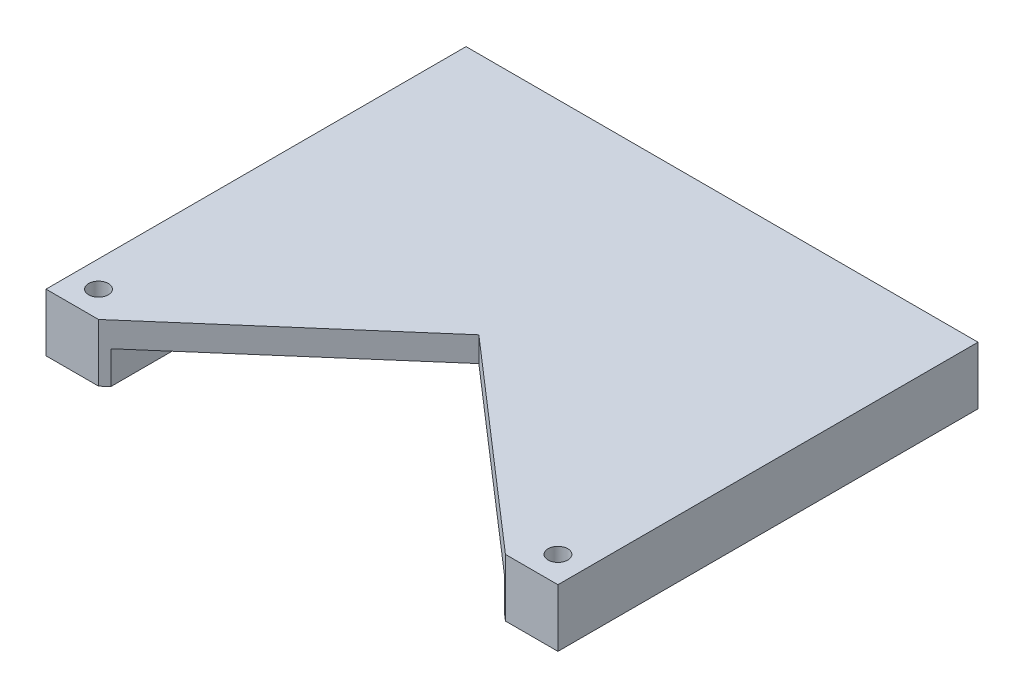
SolidWorks part; units mm, degrees
ref_plane "Front Plane" through (0, 0, 0) normal (0, 0, 1) x (1, 0, 0)
ref_plane "Top Plane" through (0, 0, 0) normal (0, 1, 0) x (1, 0, 0)
ref_plane "Right Plane" through (0, 0, 0) normal (1, 0, 0) x (0, 0, -1)
sketch "Sketch1" plane through (0, 0, 0) normal (0, 1, 0) x (1, 0, 0)
  line L1 (0, 0) -> (78, 0)
  line L2 (0, 0) -> (0, 64)
  line L3 (0, 64) -> (78, 64)
  line L4 (78, 0) -> (78, 64)
  dimension "D1" = 64
  dimension "D2" = 78
extrude "Boss-Extrude1" add sketch "Sketch1" along normal blind 8.8
sketch "Sketch2" plane through (0, 0, 0) normal (0, -1, 0) x (1, 0, 0)
  line L0 (78, -64) -> (0, -64) construction
  line L1 (6, -64) -> (72, -64)
  line L2 (6, -64) -> (6, -15)
  line L3 (6, -15) -> (72, -15)
  line L4 (72, -64) -> (72, -15)
  line L5 (0, -64) -> (0, 0) construction
  line L6 (78, 0) -> (78, -64) construction
  dimension "D1" = 6
  dimension "D2" = 6
  dimension "D3" = 49
extrude "Cut-Extrude1" cut sketch "Sketch2" against normal blind 5
sketch "Sketch3" plane through (0, 0, 0) normal (0, -1, 0) x (1, 0, 0)
  line L0 (72, -15) -> (6, -15) construction
  line L1 (9, -15) -> (69, -15)
  line L2 (9, -15) -> (9, 0)
  line L3 (9, 0) -> (69, 0)
  line L4 (69, -15) -> (69, 0)
  line L5 (0, 0) -> (78, 0) construction
  line L6 (0, -64) -> (0, 0) construction
  line L7 (78, 0) -> (78, -64) construction
  dimension "D1" = 9
  dimension "D2" = 9
extrude "Cut-Extrude2" cut sketch "Sketch3" against normal up to surface (5 mm away) up to face at (39, 5, -39.5)
sketch "Sketch4" plane through (0, 8.8, 0) normal (0, 1, 0) x (1, 0, 0)
  line L0 (0, 0) -> (78, 0) construction
  line L1 (8, 0) -> (39, 26.9479)
  line L2 (39, 26.9479) -> (70, 0)
  line L3 (39, 26.9479) -> (39, 64) construction
  line L4 (70, 0) -> (8, 0)
  line L5 (78, 64) -> (0, 64) construction
  dimension "D1" = 98
  dimension "D2" = 8
extrude "Cut-Extrude3" cut sketch "Sketch4" against normal up to next
sketch "Sketch5" plane through (0, 8.8, 0) normal (0, 1, 0) x (1, 0, 0)
  line L0 (0, 64) -> (0, 0) construction
  line L1 (0, 0) -> (8, 0) construction
  line L2 (78, 0) -> (78, 64) construction
  circle A0 centre (4, 4) radius 1.5
  circle A1 centre (74, 4) radius 1.5
  dimension "D1" = 3
  dimension "D2" = 4
  dimension "D3" = 4
  dimension "D4" = 4
extrude "Cut-Extrude4" cut sketch "Sketch5" against normal up to next
